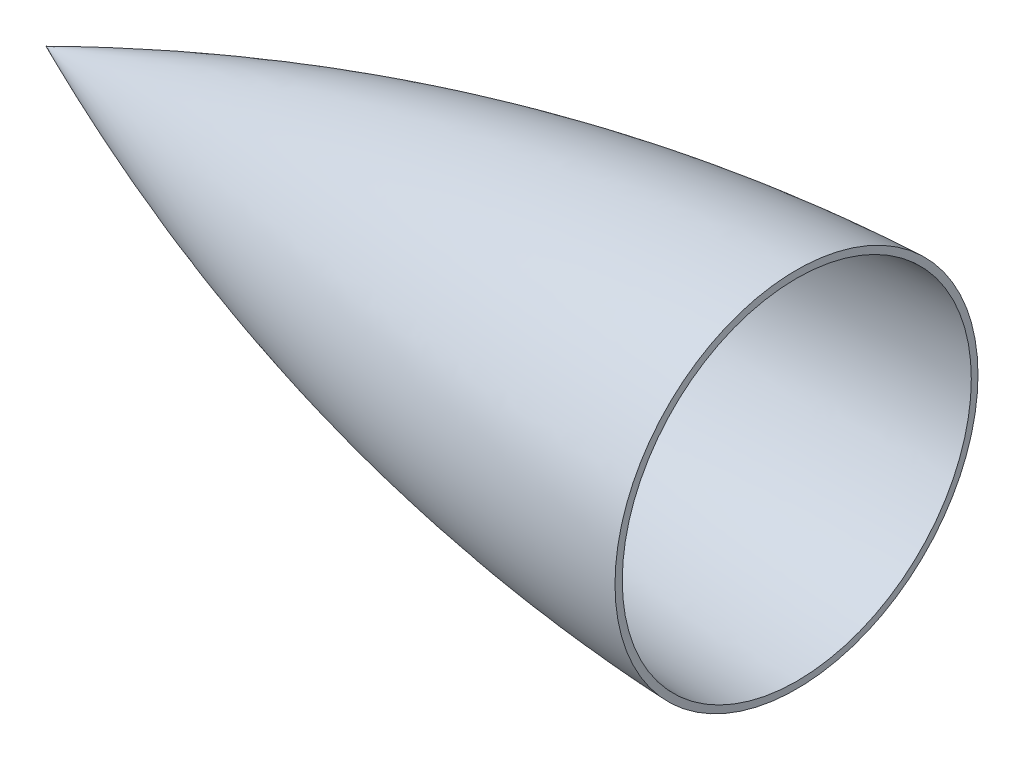
SolidWorks part; units mm, degrees
material "Hexcel AS4C (3000 Filamentos)"
ref_plane "Plano frontal" through (0, 0, 0) normal (0, 0, 1) x (1, 0, 0)
ref_plane "Plano superior" through (0, 0, 0) normal (0, 1, 0) x (1, 0, 0)
ref_plane "Plano direito" through (0, 0, 0) normal (1, 0, 0) x (0, 0, -1)
sketch "Esboço6" plane through (0, 0, 0) normal (0, 1, 0) x (1, 0, 0)
  line L0 (95.8976, 25.6218) -> (96.9869, -0.3771)
  line L1 (96.9869, -0.3771) -> (-11.6024, -0.3771)
  line L2 (96.9869, -0.3771) -> (-22.77, -0.3771) construction
  spline S0 degree 2 poles (-21.7364, -5.0453) (42.4556, 25.7347) (106.6476, 25.8573) knots 0 0 0 1 1 1 construction
  spline S1 degree 2 poles (-11.6024, -0.3771) (42.1476, 23.3697) (95.8976, 25.6218) knots 0.078935 0.078935 0.078935 0.916267 0.916267 0.916267
  point P6 (-11.6024, -0.3771)
revolve "Revolução6" add sketch "Esboço6" angle 360 about L1
shell "Casca2" thickness 1 removed face at (95.8976, 0, -25.6218)
